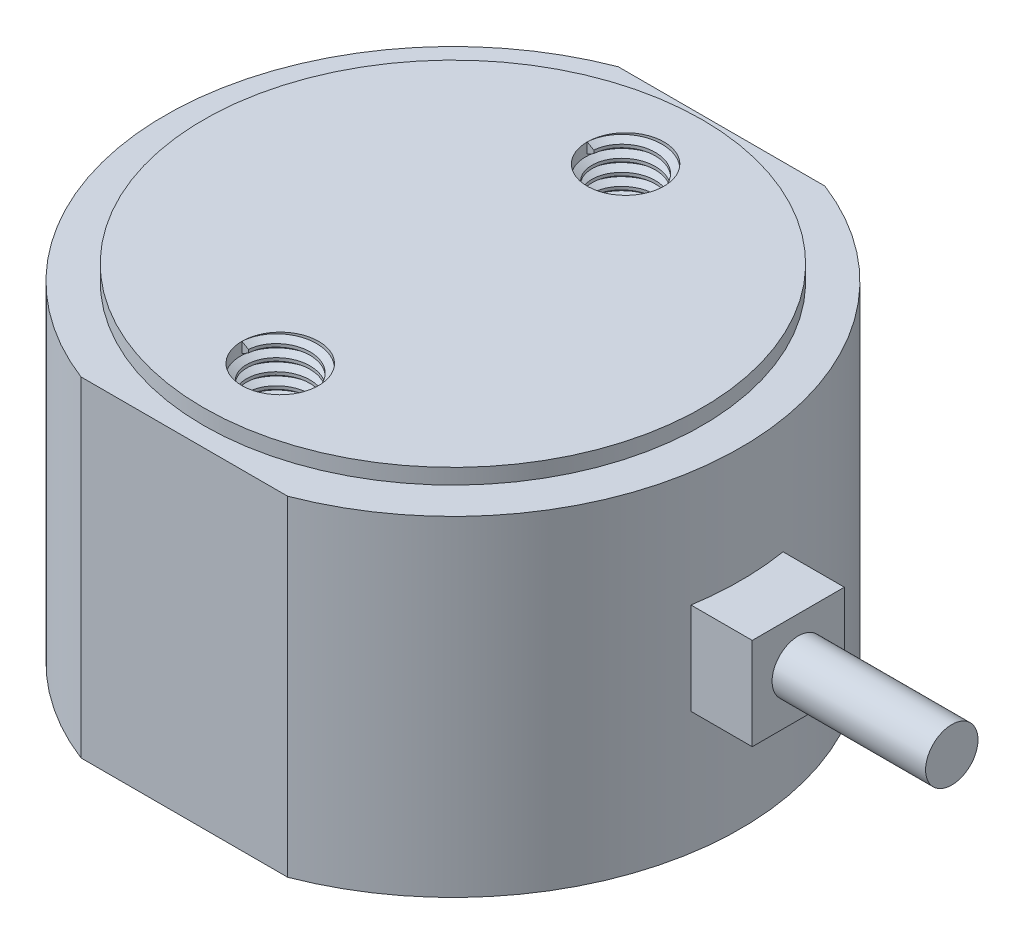
SolidWorks part; units mm, degrees
material "1.5714 (16NiCr4)"
ref_plane "前视基准面" through (0, 0, 0) normal (0, 0, 1) x (1, 0, 0)
ref_plane "上视基准面" through (0, 0, 0) normal (0, 1, 0) x (1, 0, 0)
ref_plane "右视基准面" through (0, 0, 0) normal (1, 0, 0) x (0, 0, -1)
sketch "草图1" plane through (0, 0, 0) normal (0, 1, 0) x (1, 0, 0)
  circle A0 centre (0, 0) radius 7.5
  dimension "D1" = 15
extrude "凸台-拉伸1" add sketch "草图1" along normal blind 8.6
sketch "草图2" plane through (0, 8.6, 0) normal (0, 1, 0) x (1, 0, 0)
  circle A0 centre (0, 0) radius 6.5
  dimension "D1" = 13
extrude "凸台-拉伸2" add sketch "草图2" along normal blind 0.4
sketch "草图3" plane through (0, 0, 0) normal (0, 1, 0) x (1, 0, 0)
  line L0 (0, 0) -> (0, 2.8597) construction
  line L1 (-10, 7) -> (10, 7) construction
  line L2 (-10, 7) -> (-10, -7) construction
  line L3 (-10, -7) -> (10, -7) construction
  line L4 (10, 7) -> (10, -7) construction
  line L5 (0, 0) -> (4.7889, 0) construction
  line L6 (-4.7068, -8.2507) -> (4.7068, -8.2507)
  line L7 (-4.7068, 7) -> (4.7068, 7)
  line L8 (-4.7068, 7) -> (-4.7068, 8.2507)
  line L9 (-4.7068, 8.2507) -> (4.7068, 8.2507)
  line L10 (4.7068, 7) -> (4.7068, 8.2507)
  line L11 (4.7068, -7) -> (4.7068, -8.2507)
  line L12 (-4.7068, -7) -> (4.7068, -7)
  line L13 (-4.7068, -7) -> (-4.7068, -8.2507)
  point P5 (0, 7)
  point P11 (-10, 0)
  point P16 (0, 8.2507)
  dimension "D1" = 14
  dimension "D2" = 20
  dimension "D3" = 1.2507
  dimension "D4" = 9.4137
extrude "切除-拉伸3" cut sketch "草图3" along normal through all
sketch "草图4" plane through (0, 0, 0) normal (0, 1, 0) x (1, 0, 0)
  line L0 (0, 0) -> (2.0816, 0) construction
  line L1 (0, 0) -> (0, 3.1415) construction
  circle A0 centre (0, 4.5) radius 1
  circle A1 centre (0, -4.5) radius 1
  dimension "D1" = 2
  dimension "D2" = 9
extrude "切除-拉伸6" cut sketch "草图4" along normal blind 3
thread "螺纹线1" pitch 0.3175 method extrude profile "螺纹线轮廓1" start angle 0, offset 0, length 3, pitch 0.3175, diameter 2
ref_plane "基准面1" through (1, 0, -4.5) normal (0, 0, 1) x (1, 0, 0)
sketch "螺纹线轮廓1" plane through (1, 0, -4.5) normal (0, 0, 1) x (1, 0, 0)
  line L0 (0, 0) -> (0, 0.3175) construction
  line L11 (0, 0) -> (0, 0.2778)
  line L12 (0, 0.2778) -> (-0.1719, 0.1786)
  line L13 (-0.1719, 0.1786) -> (-0.1719, 0.0992)
  line L15 (-0.1719, 0.0992) -> (0, 0)
  line L17 (-0.1719, 0.1389) -> (0, 0.1389) construction
  point P2 (0, 0)
  dimension "Pitch" = 0.3175
  dimension "Profile_Angle" = 60
  dimension "Profile_Land" = 0.0794
  dimension "Profile_Height" = 0.1719
thread "螺纹线2" pitch 0.3175 method extrude profile "螺纹线轮廓2" start angle 0, offset 0, length 3, pitch 0.3175, diameter 2
ref_plane "基准面2" through (1, 0, 4.5) normal (0, 0, 1) x (1, 0, 0)
sketch "螺纹线轮廓2" plane through (1, 0, 4.5) normal (0, 0, 1) x (1, 0, 0)
  line L0 (0, 0) -> (0, 0.3175) construction
  line L11 (0, 0) -> (0, 0.2778)
  line L12 (0, 0.2778) -> (-0.1719, 0.1786)
  line L13 (-0.1719, 0.1786) -> (-0.1719, 0.0992)
  line L15 (-0.1719, 0.0992) -> (0, 0)
  line L17 (-0.1719, 0.1389) -> (0, 0.1389) construction
  point P2 (0, 0)
  dimension "Pitch" = 0.3175
  dimension "Profile_Angle" = 60
  dimension "Profile_Land" = 0.0794
  dimension "Profile_Height" = 0.1719
sketch "草图9" plane through (0, 9, 0) normal (0, 1, 0) x (1, 0, 0)
  line L0 (0, 0) -> (3.3203, 0) construction
  line L1 (0, 0) -> (0, 3.116) construction
  circle A0 centre (0, 4.5) radius 1
  circle A1 centre (0, -4.5) radius 1
  dimension "D1" = 2
  dimension "D2" = 9
extrude "切除-拉伸7" cut sketch "草图9" against normal blind 3
thread "螺纹线3" pitch 0.3175 method extrude profile "螺纹线轮廓3" start angle 0, offset 0, length 3, pitch 0.3175, diameter 2
ref_plane "基准面3" through (-1, 9, -4.5) normal (0, 0, 1) x (-1, 0, 0)
sketch "螺纹线轮廓3" plane through (-1, 9, -4.5) normal (0, 0, 1) x (-1, 0, 0)
  line L0 (0, 0) -> (0, 0.3175) construction
  line L11 (0, 0) -> (0, 0.2778)
  line L12 (0, 0.2778) -> (-0.1719, 0.1786)
  line L13 (-0.1719, 0.1786) -> (-0.1719, 0.0992)
  line L15 (-0.1719, 0.0992) -> (0, 0)
  line L17 (-0.1719, 0.1389) -> (0, 0.1389) construction
  point P2 (0, 0)
  dimension "Pitch" = 0.3175
  dimension "Profile_Angle" = 60
  dimension "Profile_Land" = 0.0794
  dimension "Profile_Height" = 0.1719
thread "螺纹线4" pitch 0.3175 method extrude profile "螺纹线轮廓4" start angle 0, offset 0, length 3, pitch 0.3175, diameter 2
ref_plane "基准面4" through (-1, 9, 4.5) normal (0, 0, 1) x (-1, 0, 0)
sketch "螺纹线轮廓4" plane through (-1, 9, 4.5) normal (0, 0, 1) x (-1, 0, 0)
  line L0 (0, 0) -> (0, 0.3175) construction
  line L11 (0, 0) -> (0, 0.2778)
  line L12 (0, 0.2778) -> (-0.1719, 0.1786)
  line L13 (-0.1719, 0.1786) -> (-0.1719, 0.0992)
  line L15 (-0.1719, 0.0992) -> (0, 0)
  line L17 (-0.1719, 0.1389) -> (0, 0.1389) construction
  point P2 (0, 0)
  dimension "Pitch" = 0.3175
  dimension "Profile_Angle" = 60
  dimension "Profile_Land" = 0.0794
  dimension "Profile_Height" = 0.1719
sketch "草图14" plane through (0, 0, 0) normal (1, 0, 0) x (0, 0, -1)
  line L0 (-2.1868, 4.4) -> (2.4414, 4.4) construction
  line L1 (-1.2, 5.6) -> (1.2, 5.6)
  line L2 (-1.2, 5.6) -> (-1.2, 3.2)
  line L3 (-1.2, 3.2) -> (1.2, 3.2)
  line L4 (1.2, 5.6) -> (1.2, 3.2)
  line L5 (7.7, 0) -> (-7.7, 0) construction
  line L6 (0, 0) -> (0, 2.0592) construction
  point P8 (-1.2, 4.4)
  point P10 (0, 5.6)
  dimension "D1" = 4.4
  dimension "D2" = 2.4
  dimension "D3" = 2.4
extrude "凸台-拉伸3" add sketch "草图14" along normal blind 9 contours L1 L4 L3 L2
sketch "草图15" plane through (9, 0, 0) normal (1, 0, 0) x (0, 0, -1)
  circle A0 centre (0, 4.4177) radius 0.6832
extrude "凸台-拉伸4" add sketch "草图15" along normal blind 4
